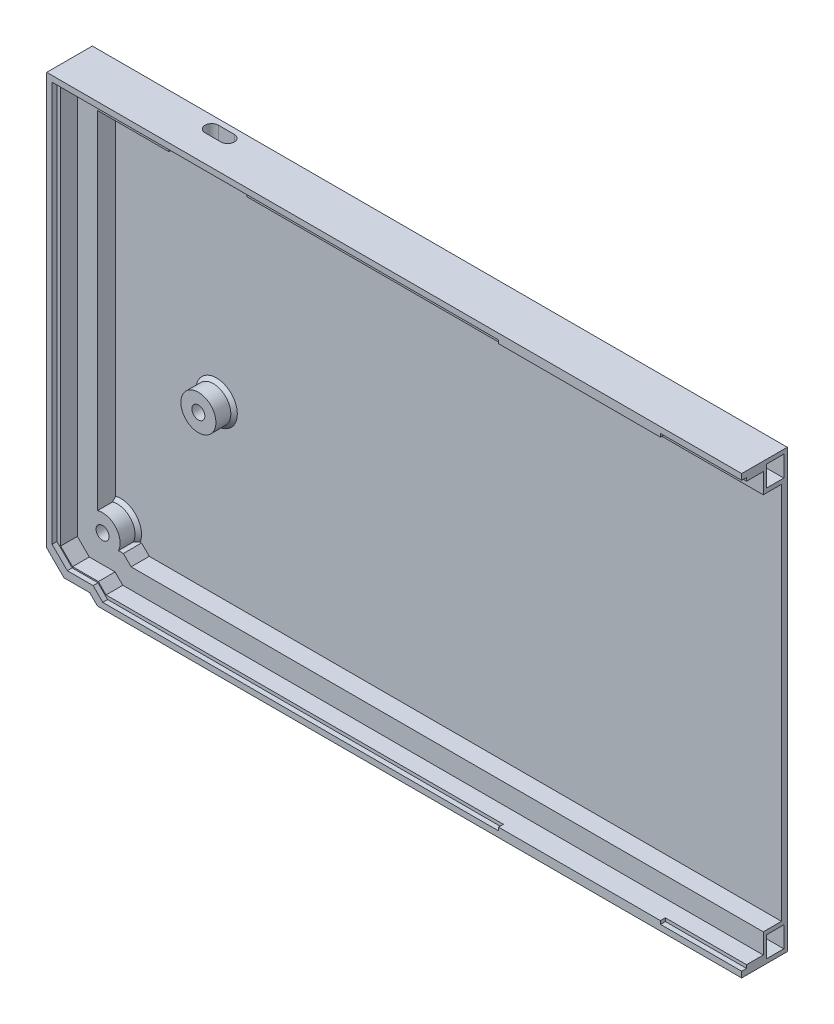
SolidWorks part; units mm, degrees
ref_plane "Přední rovina" through (0, 0, 0) normal (0, 0, 1) x (1, 0, 0)
ref_plane "Horní rovina" through (0, 0, 0) normal (0, 1, 0) x (1, 0, 0)
ref_plane "Pravá rovina" through (0, 0, 0) normal (1, 0, 0) x (0, 0, -1)
sketch "Skica3" plane through (0, 0, 0) normal (0, 0, 1) x (1, 0, 0)
  line L0 (0, 0) -> (415.1053, 0) construction
  line L1 (415.1053, 0) -> (416.6927, -1.5875) construction
  line L2 (416.6927, -1.5875) -> (416.6927, -119.8485) construction
  line L3 (0, 0) -> (-1.5875, -1.5875) construction
  line L4 (-1.5875, -1.5875) -> (-1.5875, -119.8485) construction
  line L5 (-1.5875, -119.8485) -> (0.7934, -122.2292) construction
  line L6 (0.7934, -122.2292) -> (8.7304, -122.2292) construction
  line L7 (8.7304, -122.2292) -> (11.1113, -124.61) construction
  line L8 (11.1113, -124.61) -> (403.9933, -124.61) construction
  line L9 (403.9933, -124.61) -> (406.3744, -122.2294) construction
  line L10 (406.3744, -122.2294) -> (414.3114, -122.2294) construction
  line L11 (416.6927, -119.8485) -> (414.3114, -122.2294) construction
  line L12 (2.4125, -4) -> (412.6927, -4)
  line L13 (412.6927, -4) -> (412.6927, -4)
  line L14 (412.6927, -4) -> (412.6927, -118.1914)
  line L15 (412.6927, -118.1914) -> (412.6547, -118.2294)
  line L16 (404.7177, -118.2294) -> (412.6547, -118.2294)
  line L17 (402.3367, -120.61) -> (404.7177, -118.2294)
  line L18 (12.7681, -120.61) -> (402.3367, -120.61)
  line L19 (10.3872, -118.2292) -> (12.7681, -120.61)
  line L20 (2.4502, -118.2292) -> (10.3872, -118.2292)
  line L21 (2.4125, -118.1915) -> (2.4502, -118.2292)
  line L22 (2.4125, -4) -> (2.4125, -118.1915)
  line L23 (2.4125, -4) -> (2.4125, -4)
  line L24 (-1.5875, -119.8485) -> (415.1053, 0) construction
  line L26 (0, 0) -> (416.6927, -119.8485) construction
  dimension "D1" = 135
  dimension "D2" = 135
  dimension "D3" = 4
  dimension "D4" = 2.245
  dimension "D5" = 2.245
  dimension "D6" = 118.261
  dimension "D7" = 118.261
  dimension "D8" = 3.367
  dimension "D9" = 7.937
  dimension "D10" = 3.367
  dimension "D11" = 392.882
  dimension "D12" = 3.367
  dimension "D13" = 7.937
  dimension "D14" = 3.3674
extrude "Přidat vysunutím1" add sketch "Skica3" along normal blind 5.6
shell "Skořepina1" thickness 1.8 removed face at (207.5525, -95.852, 5.6) outward yes
sketch "Skica7" plane through (0, 0, 5.6) normal (0, 0, 1) x (1, 0, 0)
  line L20 (-6.5875, 5) -> (-6.5875, -121.9196)
  line L21 (-6.5875, -121.9196) -> (-1.2775, -127.2292)
  line L22 (-1.2775, -127.2292) -> (6.6595, -127.2292)
  line L23 (6.6595, -127.2292) -> (9.0403, -129.61)
  line L24 (9.0403, -129.61) -> (406.0641, -129.61)
  line L25 (406.0641, -129.61) -> (408.4452, -127.2294)
  line L26 (408.4452, -127.2294) -> (416.3822, -127.2294)
  line L27 (416.3822, -127.2294) -> (421.6927, -121.9198)
  line L28 (421.6927, -121.9198) -> (421.6927, 5)
  line L29 (421.6927, 5) -> (-6.5875, 5)
  line L30 (-6.5875, 5) -> (-6.5875, -121.9196)
  line L31 (-6.5875, -121.9196) -> (-1.2775, -127.2292)
  line L32 (-1.2775, -127.2292) -> (6.6595, -127.2292)
  line L33 (6.6595, -127.2292) -> (9.0403, -129.61)
  line L34 (9.0403, -129.61) -> (406.0641, -129.61)
  line L35 (406.0641, -129.61) -> (408.4452, -127.2294)
  line L36 (408.4452, -127.2294) -> (416.3822, -127.2294)
  line L37 (416.3822, -127.2294) -> (421.6927, -121.9198)
  line L38 (421.6927, -121.9198) -> (421.6927, 5)
  line L39 (421.6927, 5) -> (-6.5875, 5)
  line L40 (-3.7875, 2.2) -> (-3.7875, -120.7598)
  line L41 (-3.7875, -120.7598) -> (-0.1178, -124.4292)
  line L42 (-0.1178, -124.4292) -> (7.8192, -124.4292)
  line L43 (7.8192, -124.4292) -> (10.2001, -126.81)
  line L44 (10.2001, -126.81) -> (404.9045, -126.81)
  line L45 (404.9045, -126.81) -> (407.2855, -124.4294)
  line L46 (407.2855, -124.4294) -> (415.2225, -124.4294)
  line L47 (415.2225, -124.4294) -> (418.8927, -120.7598)
  line L48 (418.8927, -120.7598) -> (418.8927, 2.2)
  line L49 (418.8927, 2.2) -> (-3.7875, 2.2)
  line L50 (-3.7875, 2.2) -> (-3.7875, -120.7598)
  line L51 (-3.7875, -120.7598) -> (-0.1178, -124.4292)
  line L52 (-0.1178, -124.4292) -> (7.8192, -124.4292)
  line L53 (7.8192, -124.4292) -> (10.2001, -126.81)
  line L54 (10.2001, -126.81) -> (404.9045, -126.81)
  line L55 (404.9045, -126.81) -> (407.2855, -124.4294)
  line L56 (407.2855, -124.4294) -> (415.2225, -124.4294)
  line L57 (415.2225, -124.4294) -> (418.8927, -120.7598)
  line L58 (418.8927, -120.7598) -> (418.8927, 2.2)
  line L59 (418.8927, 2.2) -> (-3.7875, 2.2)
  dimension "D2" = 4.4
  dimension "D1" = 7.2
extrude "Přidat vysunutím3" add sketch "Skica7" along normal blind 5.15 separate body
sketch "Skica8" plane through (0, 0, 5.6) normal (0, 0, -1) x (-1, 0, 0)
  line L0 (-421.6927, 5) -> (6.5875, 5)
  line L1 (6.5875, 5) -> (6.5875, -121.9196)
  line L2 (6.5875, 5) -> (6.5875, -121.9196) construction
  line L3 (6.5875, -121.9196) -> (1.2775, -127.2292)
  line L4 (1.2775, -127.2292) -> (-6.6595, -127.2292)
  line L5 (-6.6595, -127.2292) -> (-9.0403, -129.61)
  line L6 (-9.0403, -129.61) -> (-406.0641, -129.61)
  line L7 (-406.0641, -129.61) -> (-408.4452, -127.2294)
  line L8 (-408.4452, -127.2294) -> (-416.3822, -127.2294)
  line L9 (-416.3822, -127.2294) -> (-421.6927, -121.9198)
  line L10 (-421.6927, -121.9198) -> (-421.6927, 5)
  line L11 (-0.6125, -2.2) -> (-0.6125, -118.9371)
  line L12 (-414.4927, -2.2) -> (-0.6125, -2.2) construction
  line L13 (-0.6125, -2.2) -> (-0.6125, -118.9371) construction
  line L14 (-0.6125, -118.9371) -> (-1.7047, -120.0292)
  line L15 (-1.7047, -120.0292) -> (-9.6417, -120.0292)
  line L16 (-9.6417, -120.0292) -> (-12.0226, -122.41)
  line L17 (-12.0226, -122.41) -> (-403.0822, -122.41)
  line L18 (-403.0822, -122.41) -> (-405.4632, -120.0294)
  line L19 (-405.4632, -120.0294) -> (-413.4002, -120.0294) construction
  line L20 (-405.4632, -120.0294) -> (-413.4002, -120.0294)
  line L21 (-413.4002, -120.0294) -> (-414.4927, -118.9371) construction
  line L22 (-413.4002, -120.0294) -> (-414.4927, -118.9371)
  line L23 (-414.4927, -118.9371) -> (-414.4927, -2.2)
  line L24 (-414.4927, -2.2) -> (-0.6125, -2.2)
extrude "Přidat vysunutím4" add sketch "Skica8" along normal up to surface (7.4 mm away) up to face at (207.5525, -96.7211, -1.8)
sketch "Skica11" plane through (0, 0, 10.75) normal (0, 0, 1) x (1, 0, 0)
  line L0 (207.5526, 3.195) -> (207.5526, 5) construction
  line L1 (421.6927, 5) -> (-6.5875, 5) construction
  line L2 (207.5522, -127.805) -> (207.5522, -129.61) construction
  line L3 (9.0403, -129.61) -> (406.0641, -129.61) construction
  line L4 (-4.9474, -58.4598) -> (-6.5875, -58.4598) construction
  line L5 (-6.5875, 5) -> (-6.5875, -121.9196) construction
  line L6 (420.0526, -58.4599) -> (421.6927, -58.4599) construction
  line L7 (421.6927, -121.9198) -> (421.6927, 5) construction
  line L8 (404.9045, -126.81) -> (407.2855, -124.4294) construction
  line L9 (415.2225, -124.4294) -> (418.8927, -120.7598) construction
  line L10 (7.8192, -124.4292) -> (10.2001, -126.81) construction
  line L11 (-3.7875, -120.7598) -> (-0.1178, -124.4292) construction
  line L13 (407.2855, -124.4294) -> (415.2225, -124.4294) construction
  line L14 (-0.1178, -124.4292) -> (7.8192, -124.4292) construction
  line L30 (420.0526, 3.195) -> (-4.9474, 3.195)
  line L31 (-4.9474, 3.195) -> (-4.9474, -120.1146)
  line L32 (-4.9474, -120.1146) -> (-0.24, -124.8217)
  line L33 (-0.24, -124.8217) -> (7.697, -124.8217)
  line L34 (7.697, -124.8217) -> (10.6804, -127.805)
  line L35 (10.6804, -127.805) -> (404.4241, -127.805)
  line L36 (404.4241, -127.805) -> (406.8051, -125.4244)
  line L37 (406.8051, -125.4244) -> (414.7421, -125.4244)
  line L38 (414.7421, -125.4244) -> (420.0526, -120.1148)
  line L39 (420.0526, -120.1148) -> (420.0526, 3.195)
  line L45 (421.6927, 5) -> (-6.5875, 5)
  line L46 (-6.5875, 5) -> (-6.5875, -121.9196)
  line L47 (-6.5875, -121.9196) -> (-1.2775, -127.2292)
  line L48 (-1.2775, -127.2292) -> (6.6595, -127.2292)
  line L49 (6.6595, -127.2292) -> (9.0403, -129.61)
  line L50 (9.0403, -129.61) -> (406.0641, -129.61)
  line L51 (406.0641, -129.61) -> (408.4452, -127.2294)
  line L52 (408.4452, -127.2294) -> (416.3822, -127.2294)
  line L53 (416.3822, -127.2294) -> (421.6927, -121.9198)
  line L54 (421.6927, -121.9198) -> (421.6927, 5)
  line L55 (421.6927, 5) -> (-6.5875, 5)
  line L56 (-6.5875, 5) -> (-6.5875, -121.9196)
  line L57 (-6.5875, -121.9196) -> (-1.2775, -127.2292)
  line L58 (-1.2775, -127.2292) -> (6.6595, -127.2292)
  line L59 (6.6595, -127.2292) -> (9.0403, -129.61)
  line L60 (9.0403, -129.61) -> (406.0641, -129.61)
  line L61 (406.0641, -129.61) -> (408.4452, -127.2294)
  line L62 (408.4452, -127.2294) -> (416.3822, -127.2294)
  line L63 (416.3822, -127.2294) -> (421.6927, -121.9198)
  line L64 (421.6927, -121.9198) -> (421.6927, 5)
  point P0 (207.5523, -63.11)
  point P2 (207.5523, -63.11)
  dimension "D1" = 131
  dimension "D2" = 425
  dimension "D3" = 0
extrude "Přidat vysunutím5" add sketch "Skica11" along normal blind 1.5
sketch "Skica14" plane through (0, 0, 10.75) normal (0, 0, 1) x (1, 0, 0)
  line L0 (418.8927, 2.2) -> (-3.7875, 2.2) construction
  line L1 (182.5326, 2.2) -> (132.6326, 2.2)
  line L2 (182.5326, 2.2) -> (182.5326, 3.195)
  line L3 (182.5326, 3.195) -> (132.6326, 3.195)
  line L4 (132.6326, 2.2) -> (132.6326, 3.195)
  line L5 (420.0526, 3.195) -> (-4.9474, 3.195) construction
  line L6 (418.8927, 2.2) -> (-3.7875, 2.2) construction
  line L7 (232.5726, 2.2) -> (282.4726, 2.2)
  line L8 (232.5726, 2.2) -> (232.5726, 3.195)
  line L9 (232.5726, 3.195) -> (282.4726, 3.195)
  line L10 (282.4726, 2.2) -> (282.4726, 3.195)
  line L11 (207.5526, 3.195) -> (207.5522, -127.805) construction
  line L12 (10.6804, -127.805) -> (404.4241, -127.805) construction
  line L13 (10.2001, -126.81) -> (404.9045, -126.81) construction
  line L14 (232.5722, -126.81) -> (282.4722, -126.81)
  line L15 (232.5722, -126.81) -> (232.5722, -127.805)
  line L16 (232.5722, -127.805) -> (282.4722, -127.805)
  line L17 (282.4722, -126.81) -> (282.4722, -127.805)
  line L18 (10.6804, -127.805) -> (404.4241, -127.805) construction
  line L20 (182.5322, -126.81) -> (132.6322, -126.81)
  line L21 (182.5322, -126.81) -> (182.5322, -127.805)
  line L22 (182.5322, -127.805) -> (132.6322, -127.805)
  line L23 (132.6322, -126.81) -> (132.6322, -127.805)
  dimension "D1" = 49.9
  dimension "D2" = 49.9
  dimension "D3" = 25.02
  dimension "D4" = 25.02
  dimension "D5" = 49.9
  dimension "D6" = 49.9
  dimension "D7" = 25.02
  dimension "D8" = 25.02
extrude "Přidat vysunutím6" add sketch "Skica14" along normal up to surface (1.5 mm away) up to face at (207.5524, -100.1977, 12.25)
sketch "Skica15" plane through (0, 0, 0) normal (0, 0, 1) x (1, 0, 0)
  line L1 (34.9015, 4.5) -> (37.9015, 4.5)
  line L2 (34.9015, 4.5) -> (34.9015, -4.5)
  line L3 (34.9015, -4.5) -> (37.9015, -4.5)
  line L4 (37.9015, 4.5) -> (37.9015, -4.5)
  line L5 (34.9015, 4.5) -> (37.9015, -4.5) construction
  line L6 (34.9015, -4.5) -> (37.9015, 4.5) construction
  line L20 (-1.5875, 0) -> (-1.5875, -119.8485)
  line L21 (-1.5875, -119.8485) -> (0.7934, -122.2292)
  line L22 (0.7934, -122.2292) -> (8.7304, -122.2292)
  line L23 (8.7304, -122.2292) -> (11.1113, -124.61)
  line L24 (11.1113, -124.61) -> (403.9933, -124.61)
  line L25 (403.9933, -124.61) -> (406.3744, -122.2294)
  line L26 (406.3744, -122.2294) -> (414.3114, -122.2294)
  line L27 (414.3114, -122.2294) -> (416.6927, -119.8485)
  line L28 (416.6927, -119.8485) -> (416.6927, 0)
  line L29 (416.6927, 0) -> (-1.5875, 0)
  line L30 (-1.5875, 0) -> (-1.5875, -119.8485) construction
  line L31 (-1.5875, -119.8485) -> (0.7934, -122.2292) construction
  line L32 (0.7934, -122.2292) -> (8.7304, -122.2292) construction
  line L33 (8.7304, -122.2292) -> (11.1113, -124.61) construction
  line L34 (11.1113, -124.61) -> (403.9933, -124.61) construction
  line L35 (403.9933, -124.61) -> (406.3744, -122.2294) construction
  line L36 (406.3744, -122.2294) -> (414.3114, -122.2294) construction
  line L37 (414.3114, -122.2294) -> (416.6927, -119.8485) construction
  line L38 (416.6927, -119.8485) -> (416.6927, 0) construction
  line L39 (416.6927, 0) -> (-1.5875, 0) construction
  circle A0 centre (3.9685, -115.9542) radius 5.4
  circle A1 centre (33.4915, -69.051) radius 5.4
  circle A2 centre (411.1977, -115.8794) radius 5.4
  circle A3 centre (334.1477, -53.972) radius 5.4
  point P2 (-1.4315, -115.9542)
  point P3 (3.9685, -121.3542)
  point P4 (28.0915, -69.051)
  point P8 (33.4915, -74.451)
  point P12 (411.1977, -121.2794)
  point P13 (416.5977, -115.8794)
  point P17 (334.1477, -48.572)
  point P19 (339.5477, -53.972)
  point P21 (36.4015, 0)
  point P23 (36.4015, 0)
  dimension "D2" = 0.156
  dimension "D4" = 10.8
  dimension "D7" = 10.8
  dimension "D10" = 10.8
  dimension "D13" = 10.8
  dimension "D3" = 0.875
  dimension "D5" = 29.679
  dimension "D6" = 50.159
  dimension "D8" = 0.095
  dimension "D9" = 0.95
  dimension "D11" = 77.145
  dimension "D12" = 48.572
  dimension "D14" = 37.989
  dimension "D15" = 9
  dimension "D16" = 3
  dimension "D1" = 4
extrude "Přidat vysunutím7" add sketch "Skica15" along normal blind 5.6
sketch "Skica16" plane through (0, 0, 5.6) normal (0, 0, 1) x (1, 0, 0)
  circle A0 centre (3.9685, -115.9542) radius 2
  circle A1 centre (33.4915, -69.051) radius 2
  circle A2 centre (334.1477, -53.972) radius 2
  circle A3 centre (411.1977, -115.8794) radius 2
  dimension "D1" = 4
  dimension "D2" = 4
  dimension "D3" = 4
  dimension "D4" = 4
extrude "Odebrat vysunutím1" cut sketch "Skica16" against normal blind 5.75
chamfer "Zkosení1" distance 1 angle 45 4 edges at (407.0694, -112.3984, 0) (8.0492, -112.4175, 0) (38.8915, -69.051, 0) (339.5477, -53.972, 0)
sketch "Skica17" plane through (0, 0, 5.6) normal (0, 0, 1) x (1, 0, 0)
  line L0 (34.9015, -4.5) -> (37.9015, -4.5) construction
  line L1 (24.4015, -11.2) -> (48.4015, -11.2)
  line L2 (24.4015, -11.2) -> (24.4015, 2.2)
  line L3 (24.4015, 2.2) -> (48.4015, 2.2)
  line L4 (48.4015, -11.2) -> (48.4015, 2.2)
  line L5 (24.4015, -11.2) -> (48.4015, 2.2) construction
  line L6 (24.4015, 2.2) -> (48.4015, -11.2) construction
  line L7 (418.8927, 2.2) -> (-3.7875, 2.2) construction
  point P0 (36.4015, -4.5)
  dimension "D1" = 24
extrude "Odebrat vysunutím2" cut sketch "Skica17" against normal blind 1.6
sketch "Skica18" plane through (0, -4.5, 0) normal (0, -1, 0) x (1, 0, 0)
  line L0 (33.9515, 1.95) -> (38.8515, 1.95) construction
  line L1 (36.4015, 4) -> (36.4015, 1.95) construction
  line L2 (37.9015, 4) -> (34.9015, 4) construction
  line L3 (33.9515, 4) -> (38.8515, 4)
  line L4 (33.9515, -0.1) -> (38.8515, -0.1)
  arc A0 (33.9515, 4) -> (33.9515, -0.1) centre (33.9515, 1.95) ccw
  arc A1 (38.8515, -0.1) -> (38.8515, 4) centre (38.8515, 1.95) ccw
  point P6 (36.4015, 1.95)
  point P11 (31.9015, 1.95)
  point P12 (40.9015, 1.95)
  dimension "D1" = 9
  dimension "D3" = 2.05
  dimension "D2" = 4.1
extrude "Odebrat vysunutím3" cut sketch "Skica18" against normal up to surface (9.5 mm away) up to face at (207.5526, 5, 5.225)
sketch "Skica23" plane through (-6.5875, 0, 0) normal (-1, 0, 0) x (0, 0, 1)
  line L2 (-1.8, 5) -> (-1.8, -121.9196) construction
  line L4 (-1.8, -58.4598) -> (12.25, -58.4598) construction
  line L5 (12.25, 5) -> (12.25, -121.9196) construction
  circle A0 centre (3.2, -18.4598) radius 2
  circle A1 centre (3.2, -98.4598) radius 2
  point P8 (-1.8, -58.4598)
  dimension "D2" = 4
  dimension "D3" = 4
  dimension "D1" = 40
  dimension "D4" = 5
extrude "Odebrat vysunutím4" cut sketch "Skica23" against normal blind 5.7
sketch "Skica24" plane through (421.6927, 0, 0) normal (1, 0, 0) x (0, 0, -1)
  line L0 (1.8, -58.4599) -> (-12.25, -58.4599) construction
  line L1 (1.8, -121.9198) -> (1.8, 5) construction
  line L2 (-12.25, -121.9198) -> (-12.25, 5) construction
  circle A0 centre (-3.2, -18.4599) radius 2
  circle A1 centre (-3.2, -98.4599) radius 2
  dimension "D1" = 4
  dimension "D2" = 4
  dimension "D3" = 40
  dimension "D4" = 5
extrude "Odebrat vysunutím5" cut sketch "Skica24" against normal blind 5.7
sketch "Skica25" plane through (0, 0, -1.8) normal (0, 0, -1) x (-1, 0, 0)
  line L0 (-421.6927, -121.9198) -> (-421.6927, 5) construction
  line L1 (-421.6927, 5) -> (6.5875, 5) construction
  line L2 (6.5875, 5) -> (6.5875, -121.9196) construction
  line L3 (-9.0403, -129.61) -> (-406.0641, -129.61) construction
  circle A0 centre (-401.6927, -15) radius 6.25
  circle A1 centre (-13.4125, -15) radius 6.25
  circle A2 centre (-388.4452, -109.61) radius 6.25
  circle A3 centre (-26.6595, -109.61) radius 6.25
  dimension "D1" = 12.5
  dimension "D2" = 12.5
  dimension "D3" = 12.5
  dimension "D4" = 12.5
  dimension "D5" = 20
  dimension "D6" = 20
  dimension "D7" = 20
  dimension "D8" = 20
  dimension "D9" = 20
  dimension "D10" = 20
  dimension "D11" = 20
  dimension "D12" = 20
extrude "Odebrat vysunutím6" cut sketch "Skica25" against normal blind 1.2
sketch "Skica26" plane through (0, 5, 0) normal (0, 1, 0) x (1, 0, 0)
  line L0 (207.5526, 1.8) -> (207.5526, -12.25)
  line L1 (421.6927, 1.8) -> (-6.5875, 1.8) construction
  line L2 (421.6927, -12.25) -> (-6.5875, -12.25) construction
  line L3 (207.5526, -12.25) -> (421.6927, -12.25)
  line L4 (421.6927, -12.25) -> (421.6927, 1.8)
  line L5 (421.6927, 1.8) -> (207.5526, 1.8)
extrude "Odebrat vysunutím7" cut sketch "Skica26" against normal through all
sketch "Skica27" plane through (207.5526, 0, 0) normal (1, 0, 0) x (0, 0, -1)
  line L0 (0, -4) -> (1.8, -4) construction
  line L1 (1.8, -129.61) -> (1.8, 5) construction
  line L2 (-5.6, 2.2) -> (-5.6, 5) construction
  line L3 (1.8, 5) -> (-12.25, 5) construction
  line L4 (0, -120.61) -> (1.8, -120.61) construction
  line L5 (-5.6, -126.81) -> (-5.6, -129.61) construction
  line L6 (1.8, -129.61) -> (-12.25, -129.61) construction
  line L7 (-5.6, -129.61) -> (1.8, -120.61) construction
  line L8 (-5.6, -120.61) -> (1.8, -129.61) construction
  line L9 (-5.6, -4) -> (1.8, 5) construction
  line L10 (-5.6, 5) -> (1.8, -4) construction
  line L11 (0, -120.61) -> (-5.6, -120.61) construction
  line L12 (-4.5311, -2.7) -> (0.7311, -2.7)
  line L13 (-4.5311, -2.7) -> (-4.5311, 3.7)
  line L14 (-4.5311, 3.7) -> (0.7311, 3.7)
  line L15 (0.7311, -2.7) -> (0.7311, 3.7)
  line L16 (-4.5311, -2.7) -> (0.7311, 3.7) construction
  line L17 (-4.5311, 3.7) -> (0.7311, -2.7) construction
  line L18 (-4.5311, -128.31) -> (0.7311, -128.31)
  line L19 (-4.5311, -128.31) -> (-4.5311, -121.91)
  line L20 (-4.5311, -121.91) -> (0.7311, -121.91)
  line L21 (0.7311, -128.31) -> (0.7311, -121.91)
  line L22 (-4.5311, -128.31) -> (0.7311, -121.91) construction
  line L23 (-4.5311, -121.91) -> (0.7311, -128.31) construction
  point P25 (-1.9, 0.5)
  point P30 (-1.9, -125.11)
  dimension "D1" = 1.3
  dimension "D2" = 1.3
extrude "Odebrat vysunutím8" cut sketch "Skica27" against normal blind 17
